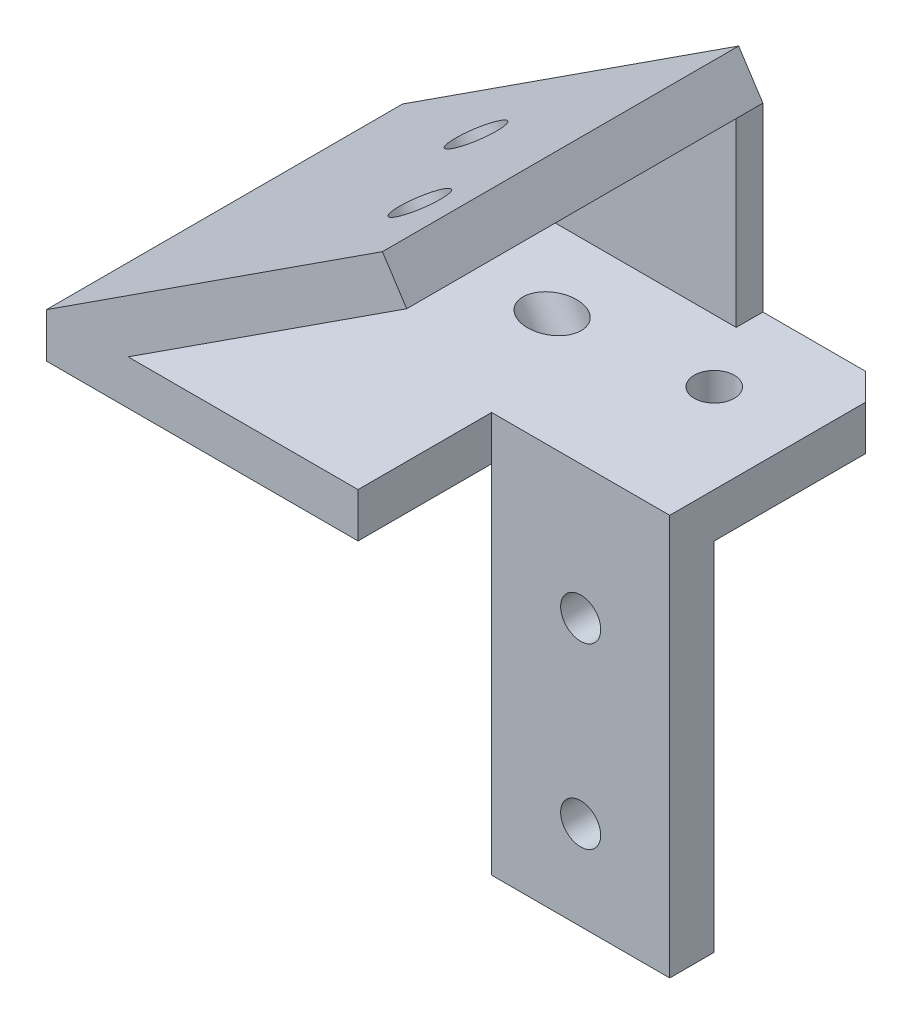
SolidWorks part; units mm, degrees
ref_plane "Front Plane" through (0, 0, 0) normal (0, 0, 1) x (1, 0, 0)
ref_plane "Top Plane" through (0, 0, 0) normal (0, 1, 0) x (1, 0, 0)
ref_plane "Right Plane" through (0, 0, 0) normal (1, 0, 0) x (0, 0, -1)
sketch "Sketch1" plane through (0, 0, 0) normal (0, 1, 0) x (1, 0, 0)
  line L0 (0, 10) -> (20, 10) construction
  line L1 (0, 0) -> (20, 0)
  line L2 (0, 0) -> (0, 20)
  line L3 (0, 20) -> (20, 20)
  line L4 (20, 0) -> (20, 20)
  circle A0 centre (10, 10) radius 2.25
  dimension "D3" = 4.5
  dimension "D1" = 20
  dimension "D2" = 20
extrude "Boss-Extrude1" add sketch "Sketch1" along normal blind 5
sketch "Sketch2" plane through (0, 0, 0) normal (0, 0, 1) x (1, 0, 0)
  line L0 (20, 5) -> (20, 0) construction
  line L1 (0, 5) -> (20, 5)
  line L2 (0, 5) -> (0, -40)
  line L3 (0, -40) -> (20, -40)
  line L4 (20, 5) -> (20, -40)
  line L5 (0, 0) -> (20, 0) construction
  line L6 (0, -30) -> (20, -30) construction
  line L7 (0, -10) -> (20, -10) construction
  circle A0 centre (10, -30) radius 2.25
  circle A1 centre (10, -10) radius 2.25
  dimension "D2" = 4.5
  dimension "D1" = 40
  dimension "D3" = 10
  dimension "D4" = 20
extrude "Boss-Extrude2" add sketch "Sketch2" along normal blind 5
chamfer "Chamfer1" distance 3 angle 45 1 edges at (20, 2.5, -20)
sketch "Sketch3" plane through (0, 0, 0) normal (-1, 0, 0) x (0, 0, 1)
  line L0 (-20, 0) -> (0, 0) construction
  line L1 (-20, 5) -> (20, 5)
  line L2 (-20, 5) -> (-20, 0)
  line L3 (-20, 0) -> (20, 0)
  line L4 (20, 5) -> (20, 0)
  dimension "D1" = 40
extrude "Boss-Extrude3" add sketch "Sketch3" along normal blind 35
sketch "Sketch4" plane through (0, 0, 20) normal (0, 0, 1) x (1, 0, 0)
  line L0 (-35, 5) -> (2.7402, 29.5088)
  line L1 (5.4634, 25.3154) -> (-25.8196, 5)
  line L2 (-35, 5) -> (0, 5) construction
  line L3 (-35, 5) -> (-25.8196, 5)
  line L7 (2.7402, 29.5088) -> (5.4634, 25.3154)
  dimension "D1" = 5
  dimension "D2" = 33
  dimension "D3" = 45
  dimension "D4" = 90
extrude "Boss-Extrude4" add sketch "Sketch4" against normal blind 40
sketch "Sketch5" plane through (0, 0, -20) normal (0, 0, -1) x (-1, 0, 0)
  line L0 (-5.4634, 25.3154) -> (-5.4634, 5)
  line L1 (-17, 5) -> (25.8196, 5) construction
  line L2 (-5.4634, 5) -> (25.8196, 5)
  line L3 (25.8196, 5) -> (-5.4634, 25.3154)
extrude "Boss-Extrude5" add sketch "Sketch5" against normal blind 3
sketch "Sketch6" plane through (-12.666, 19.5039, 0) normal (-0.5446, 0.8387, 0) x (0.8387, 0.5446, 0)
  line L0 (18.3697, 20) -> (18.3697, -20) construction
  line L2 (18.3697, -20) -> (-26.6303, -20) construction
  circle A0 centre (9.3697, -8.25) radius 2.75
  circle A1 centre (-2.4803, 8) radius 2.75
  dimension "D1" = 5.5
  dimension "D2" = 9
  dimension "D3" = 11.75
  dimension "D4" = 28
  dimension "D5" = 20.85
extrude "Cut-Extrude1" cut sketch "Sketch6" against normal through all
